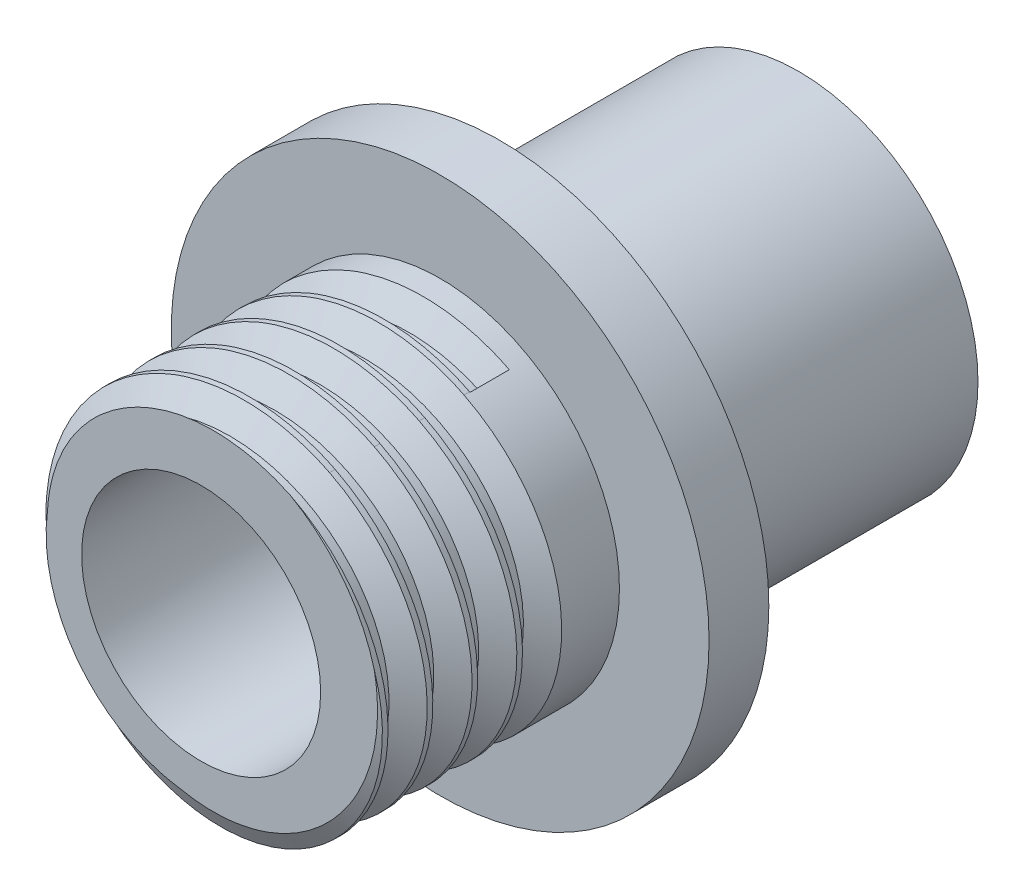
SolidWorks part; units mm, degrees
ref_plane "Plano frontal" through (0, 0, 0) normal (0, 0, 1) x (1, 0, 0)
ref_plane "Plano superior" through (0, 0, 0) normal (0, 1, 0) x (1, 0, 0)
ref_plane "Plano direito" through (0, 0, 0) normal (1, 0, 0) x (0, 0, -1)
sketch "Esboço1" plane through (0, 0, 0) normal (0, 0, 1) x (1, 0, 0)
  circle A1 centre (0, 0) radius 6
  dimension "D1" = 12
extrude "Ressalto-extrusão1" add sketch "Esboço1" along normal blind 20 contours A1
sketch "Esboço3" plane through (0, 0, 0) normal (0, 1, 0) x (1, 0, 0)
  line L0 (0, -20) -> (0, 49980) construction
  line L1 (-6, -20) -> (6, -20) construction
  line L2 (6, -20) -> (6, 0) construction
  line L3 (6, -10) -> (9, -10)
  line L4 (6, -10) -> (6, -12)
  line L5 (6, -12) -> (9, -12)
  line L6 (9, -10) -> (9, -12)
  line L7 (6, -10) -> (9, -12) construction
  line L8 (6, -12) -> (9, -10) construction
  line L9 (6, 0) -> (-6, 0) construction
  point P4 (0, -20)
  point P10 (7.5, -11)
  dimension "D1" = 10
  dimension "D2" = 2
  dimension "D3" = 3
revolve "Revolução1" add sketch "Esboço3" angle 360 about L0
sketch "Esboço4" plane through (0, 0, 20) normal (0, 0, 1) x (1, 0, 0)
  circle A0 centre (0, 0) radius 4
  dimension "D1" = 8
extrude "Corte-extrusão1" cut sketch "Esboço4" against normal through all
thread "Rosca1" pitch 1.5 method cut profile "Perfil da rosca1" start angle 0, offset 2, length 8, pitch 1.5, diameter 12
ref_plane "Plano1" through (-6, 0, 22) normal (0, -1, 0) x (-1, 0, 0)
sketch "Perfil da rosca1" plane through (-6, 0, 22) normal (0, -1, 0) x (-1, 0, 0)
  line L0 (0, 0) -> (0, 1.5) construction
  line L11 (0, 0) -> (0, 1.3125)
  line L12 (0, 1.3125) -> (-0.8119, 0.8437)
  line L13 (-0.8119, 0.8437) -> (-0.8119, 0.4687)
  line L15 (-0.8119, 0.4687) -> (0, 0)
  line L17 (-0.8119, 0.6562) -> (0, 0.6562) construction
  point P2 (0, 0)
  dimension "Pitch" = 1.5
  dimension "Profile_Angle" = 60
  dimension "Profile_Land" = 0.375
  dimension "Profile_Height" = 0.8119
